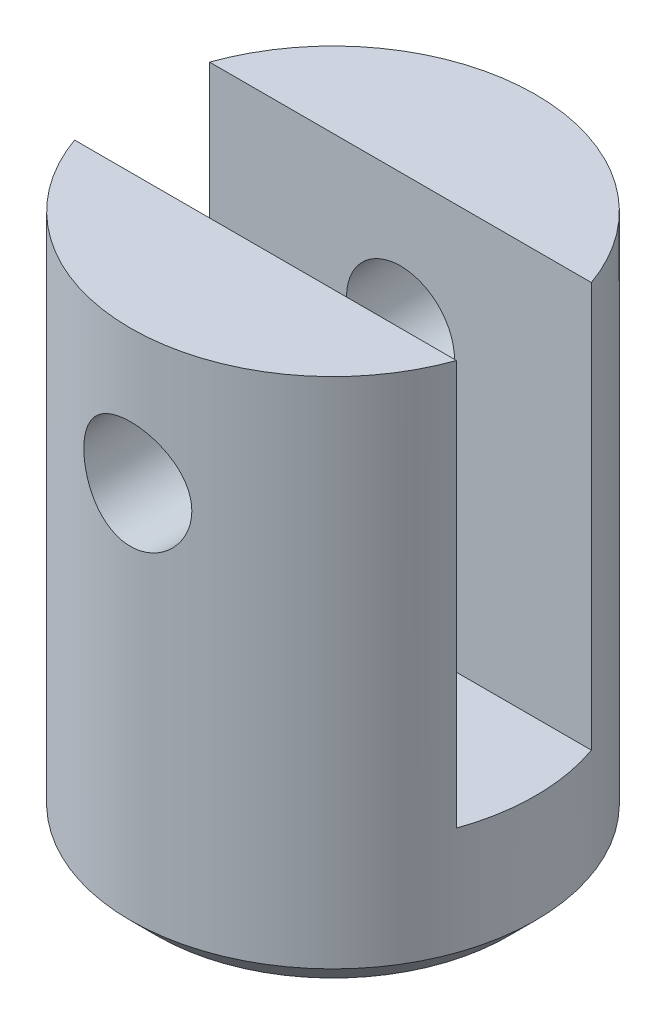
SolidWorks part; units mm, degrees
material "Aço cromo inoxidável"
ref_plane "Plano frontal" through (0, 0, 0) normal (0, 0, 1) x (1, 0, 0)
ref_plane "Plano superior" through (0, 0, 0) normal (0, 1, 0) x (1, 0, 0)
ref_plane "Plano direito" through (0, 0, 0) normal (1, 0, 0) x (0, 0, -1)
sketch "Esboço1" plane through (0, 0, 0) normal (0, 1, 0) x (1, 0, 0)
  circle A0 centre (0, 0) radius 7.5
  dimension "D1" = 15
extrude "Ressalto-extrusão1" add sketch "Esboço1" along normal mid plane 20
sketch "Esboço2" plane through (0, 0, 0) normal (1, 0, 0) x (0, 0, -1)
  line L0 (7.5, 10) -> (-7.5, 10) construction
  line L1 (-2.5, 10) -> (2.5, 10)
  line L2 (-2.5, 10) -> (-2.5, -5)
  line L3 (-2.5, -5) -> (2.5, -5)
  line L4 (2.5, 10) -> (2.5, -5)
  line L5 (0, -5) -> (0, 10) construction
  line L6 (-2.5, 2.5) -> (2.5, 2.5) construction
  point P6 (0, 0)
  point P7 (2.3219, -1.0163)
  point P568 (0, 2.5)
  dimension "D1" = 15
  dimension "D2" = 5
extrude "Corte-extrusão1" cut sketch "Esboço2" against normal through all both and the other way through all
sketch "Esboço3" plane through (0, 0, 0) normal (0, 0, 1) x (1, 0, 0)
  line L0 (0, 10) -> (0, 5) construction
  line L1 (7.0711, 10) -> (-7.0711, 10) construction
  circle A0 centre (0, 5) radius 2
  dimension "D1" = 4
  dimension "D2" = 5
extrude "Corte-extrusão2" cut sketch "Esboço3" against normal through all both and the other way through all
chamfer "Chanfro1" distance 1 angle 45 1 edges at (0, -10, 7.5)
